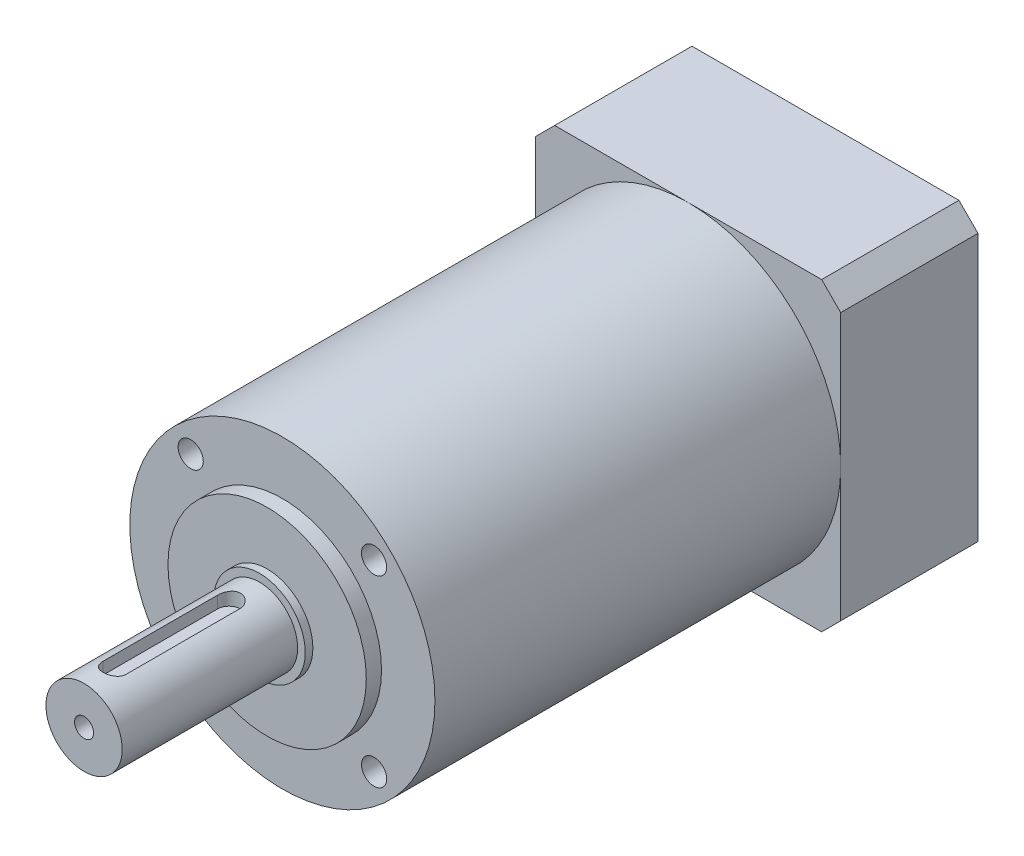
SolidWorks part; units mm, degrees
ref_plane "Front" through (0, 0, 0) normal (0, 0, 1) x (1, 0, 0)
ref_plane "Top" through (0, 0, 0) normal (0, 1, 0) x (1, 0, 0)
ref_plane "Right" through (0, 0, 0) normal (1, 0, 0) x (0, 0, -1)
sketch "Эскиз1" plane through (0, 0, 0) normal (0, 0, 1) x (1, 0, 0)
  line L1 (0, 0) -> (40, 0)
  line L2 (0, 0) -> (0, 40)
  line L3 (0, 40) -> (40, 40)
  line L4 (40, 0) -> (40, 40)
  dimension "D1" = 40
  dimension "D2" = 40
extrude "Бобышка-Вытянуть1" add sketch "Эскиз1" along normal blind 18
sketch "Эскиз2" plane through (0, 0, 18) normal (0, 0, 1) x (1, 0, 0)
  line L1 (0, 0) -> (40, 0) construction
  line L2 (40, 0) -> (40, 40) construction
  circle A0 centre (20, 20) radius 20
  dimension "D1" = 40
extrude "Бобышка-Вытянуть2" add sketch "Эскиз2" along normal blind 53.2
sketch "Эскиз3" plane through (0, 0, 71.2) normal (0, 0, 1) x (1, 0, 0)
  circle A0 centre (20, 20) radius 13
  arc A1 (40, 20) -> (20, 40) centre (20, 20) ccw construction
  dimension "D1" = 26
extrude "Бобышка-Вытянуть3" add sketch "Эскиз3" along normal blind 2
sketch "Эскиз4" plane through (0, 0, 73.2) normal (0, 0, 1) x (1, 0, 0)
  circle A0 centre (20, 20) radius 6
  circle A1 centre (20, 20) radius 13 construction
  dimension "D1" = 12
extrude "Бобышка-Вытянуть4" add sketch "Эскиз4" along normal blind 1
sketch "Эскиз5" plane through (0, 0, 74.2) normal (0, 0, 1) x (1, 0, 0)
  circle A0 centre (20, 20) radius 5
  circle A1 centre (20, 20) radius 6 construction
  dimension "D1" = 10
extrude "Бобышка-Вытянуть5" add sketch "Эскиз5" along normal blind 23 contours A0
ref_plane "Плоскость3" through (0, 25, 0) normal (0, -1, 0) x (-1, 0, 0)
sketch "Эскиз9" plane through (0, 25, 0) normal (0, -1, 0) x (-1, 0, 0)
  line L0 (-20, -93.2) -> (-20, -78.2) construction
  line L1 (-21.5, -93.2) -> (-21.5, -78.2)
  line L2 (-18.5, -93.2) -> (-18.5, -78.2)
  line L3 (-25, -97.2) -> (-15, -97.2) construction
  arc A0 (-21.5, -93.2) -> (-18.5, -93.2) centre (-20, -93.2) ccw
  arc A1 (-18.5, -78.2) -> (-21.5, -78.2) centre (-20, -78.2) ccw
  point P2 (-20, -85.7)
  dimension "D2" = 1.5
  dimension "D1" = 15
  dimension "D3" = 4
  dimension "D4" = 20
extrude "Вырез-Вытянуть1" cut sketch "Эскиз9" along normal blind 1.8
hole_wizard "Отверстие обработанное метчиком M31" positions "Эскиз11" profile "Эскиз10" tap size "M3" standard "DIN"
sketch "Эскиз11" plane through (0, 0, 97.2) normal (0, 0, 1) x (1, 0, 0)
  circle A0 centre (20, 20) radius 6 construction
  point P0 (20, 20)
sketch "Эскиз10" plane through (20, 20, 97.2) normal (1, 0, 0) x (0, -1, 0)
  line L0 (0, 0) -> (0, 15.7511)
  line L1 (0, 15.7511) -> (1.25, 15)
  line L2 (1.25, 15) -> (1.25, 0)
  line L5 (1.25, 0) -> (0, 0)
  line L10 (0, 15.7511) -> (-1.25, 15) construction
  line L11 (0, -6.35) -> (0, 107.95) construction
  dimension "Диаметр сверла" = 2.5
  dimension "Глубина сверла" = 15
  dimension "Угол заточки сверла" = 118
cosmetic thread "Отверстие резьбы1" parameters "D1"=10, "D2"=3
sketch "Эскиз12" plane through (0, 0, 71.2) normal (0, 0, 1) x (1, 0, 0)
  line L0 (7.9792, 32.0208) -> (20, 20)
  line L1 (20, 20) -> (3, 20)
  circle A0 centre (20, 20) radius 17
  point P3 (7.9792, 32.0208)
  dimension "D1" = 34
  dimension "D2" = 45
hole_wizard "Отверстие обработанное метчиком M41" positions "Эскиз13" profile "Эскиз14" tap size "M4" standard "DIN"
sketch "Эскиз13" plane through (0, 0, 71.2) normal (0, 0, 1) x (1, 0, 0)
  point P0 (7.9792, 32.0208)
sketch "Эскиз14" plane through (7.9792, 32.0208, 71.2) normal (1, 0, 0) x (0, -1, 0)
  line L0 (0, 0) -> (0, 7.9914)
  line L1 (0, 7.9914) -> (1.65, 7)
  line L2 (1.65, 7) -> (1.65, 0)
  line L5 (1.65, 0) -> (0, 0)
  line L10 (0, 7.9914) -> (-1.65, 7) construction
  line L11 (0, -6.35) -> (0, 107.95) construction
  dimension "Диаметр сверла" = 3.3
  dimension "Глубина сверла" = 7
  dimension "Угол заточки сверла" = 118
cosmetic thread "Отверстие резьбы2" parameters "D1"=7, "D2"=4
pattern_circular "Круговой массив1" count 4 over 360 about axis through (20, 20, 71.2) along (0, 0, 1) of "Отверстие обработанное метчиком M41"
cosmetic thread "Отверстие резьбы3" parameters "D1"=7, "D2"=4
cosmetic thread "Отверстие резьбы4" parameters "D1"=7, "D2"=4
cosmetic thread "Отверстие резьбы5" parameters "D1"=7, "D2"=4
chamfer "Фаска1" distance 2.5 angle 45 4 edges at (0, 0, 9) (40, 0, 9) (40, 40, 9) (0, 40, 9)
sketch "Эскиз15" plane through (0, 0, 0) normal (0, 0, -1) x (-1, 0, 0)
  circle A0 centre (-20, 20) radius 16.5
  dimension "D3" = 33
  dimension "D1" = 20
  dimension "D2" = 20
extrude "Вырез-Вытянуть2" cut sketch "Эскиз15" against normal blind 18
sketch "Эскиз16" plane through (0, 0, 18) normal (0, 0, -1) x (-1, 0, 0)
  line L3 (-21, 14.5917) -> (-21, 11.0557)
  line L5 (-19, 14.5917) -> (-19, 11.0557)
  arc A0 (-19, 14.5917) -> (-21, 14.5917) centre (-20, 20) ccw
  arc A1 (-19, 11.0557) -> (-21, 11.0557) centre (-20, 20) ccw
  dimension "D1" = 11
  dimension "D2" = 18
  dimension "D3" = 20
  dimension "D4" = 20
  dimension "D5" = 2
  dimension "D6" = 19
extrude "Бобышка-Вытянуть6" add sketch "Эскиз16" along normal blind 15
fillet "Скругление1" radius 0.5 2 edges at (20, 25.5, 3) (20, 29, 3)
sketch "Эскиз17" plane through (0, 0, 18) normal (0, 0, -1) x (-1, 0, 0)
  circle A0 centre (-20, 20) radius 9
  circle A1 centre (-20, 20) radius 13.5
  dimension "D1" = 27
  dimension "D2" = 18
extrude "Бобышка-Вытянуть7" add sketch "Эскиз17" along normal blind 16
fillet "Скругление2" radius 0.5 1 edges at (11, 20, 2)
sketch "Эскиз18" plane through (0, 0, 0) normal (0, 0, -1) x (-1, 0, 0)
  line L0 (-36.3, 36.3) -> (-20, 20)
  line L2 (-2.5, 0) -> (0, 2.5) construction
  line L3 (-1.25, 1.25) -> (-38.75, 1.25)
  line L4 (-40, 2.5) -> (-37.5, 0) construction
  line L5 (-20, 20) -> (-36.3, 36.3)
  line L7 (-36.3, 36.3) -> (-32.6, 40)
  line L8 (-37.5, 40) -> (-2.5, 40) construction
  line L9 (-32.6, 40) -> (-36.3, 36.3)
  point P0 (-36.3, 36.3)
  point P1 (-20, 20)
  dimension "D1" = 16.3
  dimension "D2" = 16.3
hole_wizard "Отверстие обработанное метчиком M43" positions "Эскиз21" profile "Эскиз22" tap size "M4" standard "DIN"
sketch "Эскиз21" plane through (0, 0, 0) normal (0, 0, -1) x (-1, 0, 0)
  point P0 (-36.3, 36.3)
sketch "Эскиз22" plane through (36.3, 36.3, 0) normal (1, 0, 0) x (0, 1, 0)
  line L0 (0, 0) -> (0, 12.4914)
  line L1 (0, 12.4914) -> (1.65, 11.5)
  line L2 (1.65, 11.5) -> (1.65, 0)
  line L5 (1.65, 0) -> (0, 0)
  line L10 (0, 12.4914) -> (-1.65, 11.5) construction
  line L11 (0, -6.35) -> (0, 107.95) construction
  dimension "Диаметр сверла" = 3.3
  dimension "Глубина сверла" = 11.5
  dimension "Угол заточки сверла" = 118
cosmetic thread "Отверстие резьбы7" parameters "D1"=8, "D2"=4
pattern_circular "Круговой массив2" count 4 over 360 about axis through (20, 20, 18) along (0, 0, -1) of "Отверстие обработанное метчиком M43"
cosmetic thread "Отверстие резьбы8" parameters "D1"=8, "D2"=4
cosmetic thread "Отверстие резьбы9" parameters "D1"=8, "D2"=4
cosmetic thread "Отверстие резьбы10" parameters "D1"=8, "D2"=4
